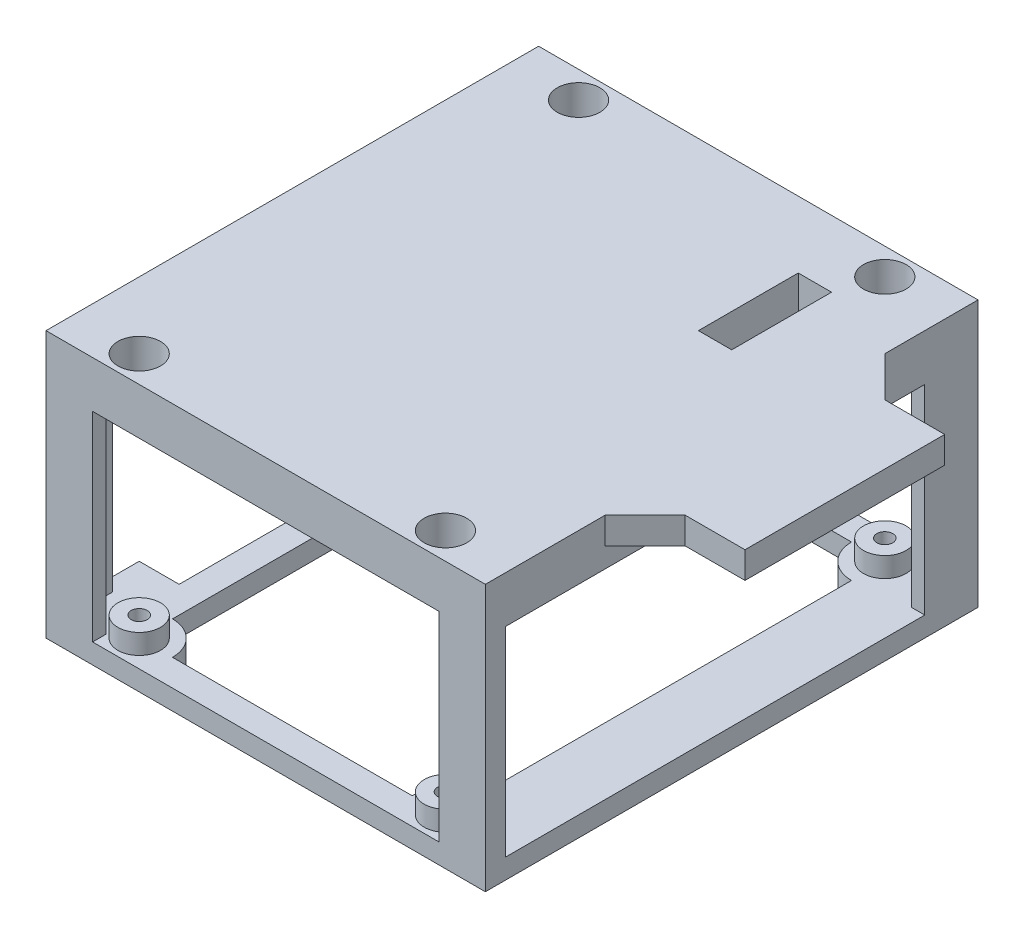
SolidWorks part; units mm, degrees
ref_plane "Front Plane" through (0, 0, 0) normal (0, 0, 1) x (1, 0, 0)
ref_plane "Top Plane" through (0, 0, 0) normal (0, 1, 0) x (1, 0, 0)
ref_plane "Right Plane" through (0, 0, 0) normal (1, 0, 0) x (0, 0, -1)
sketch "Sketch1" plane through (0, 0, 0) normal (0, 1, 0) x (1, 0, 0)
  line L0 (56, 70) -> (56, 4) construction
  line L1 (0, 0) -> (66, 0)
  line L2 (0, 0) -> (0, 74)
  line L3 (0, 74) -> (66, 74)
  line L4 (66, 0) -> (66, 74)
  line L5 (10, 4) -> (56, 4) construction
  line L6 (15, 70) -> (51, 70)
  line L11 (10, 65) -> (10, 9)
  line L12 (15, 4) -> (51, 4)
  line L13 (56, 65) -> (56, 9)
  line L14 (33, 74) -> (33, 0) construction
  line L19 (66, 54) -> (81, 54)
  line L20 (66, 54) -> (66, 24)
  line L21 (66, 24) -> (81, 24)
  line L22 (81, 54) -> (81, 24)
  line L23 (49, 64) -> (54, 64)
  line L24 (49, 64) -> (49, 49)
  line L25 (49, 49) -> (54, 49)
  line L26 (54, 64) -> (54, 49)
  line L28 (0, 60) -> (6, 60)
  line L29 (0, 60) -> (0, 14)
  line L30 (0, 14) -> (6, 14)
  line L31 (6, 60) -> (6, 14)
  circle A0 centre (10, 70) radius 1.2
  circle A1 centre (56, 70) radius 1.2
  circle A2 centre (10, 4) radius 1.2
  circle A3 centre (56, 4) radius 1.2
  circle A4 centre (10, 70) radius 3.2
  circle A5 centre (56, 70) radius 3.2
  circle A6 centre (10, 4) radius 3.2
  circle A7 centre (56, 4) radius 3.2
  arc A8 (10, 65) -> (15, 70) centre (10, 70) ccw
  arc A9 (51, 70) -> (56, 65) centre (56, 70) ccw
  arc A10 (56, 9) -> (51, 4) centre (56, 4) ccw
  arc A11 (15, 4) -> (10, 9) centre (10, 4) ccw
  point P13 (56, 37)
  point P14 (66, 37)
  point P15 (33, 4)
  point P16 (33, 0)
  dimension "D3" = 2.4
  dimension "D4" = 46
  dimension "D5" = 66
  dimension "D6" = 6.4
  dimension "D7" = 20
  dimension "D8" = 30
  dimension "D9" = 2
  dimension "D12" = 5
  dimension "D1" = 66
  dimension "D2" = 74
  dimension "D10" = 46
  dimension "D11" = 66
  dimension "D13" = 5
  dimension "D14" = 16
  dimension "D15" = 15
  dimension "D16" = 15
  dimension "D17" = 10
  dimension "D18" = 14
  dimension "D19" = 14
  dimension "D20" = 6
extrude "Main Outer Connection" add sketch "Sketch1" along normal blind 40 contours L1 L4 L3 L2 A3 A2 A1 A0 L12 A11 L11 A8 L6 A9 L13 A10 | A6 A2 | A7 A3 | A4 A0 | A5 A1 | L6 A9 L13 A10 L12 A11 L11 A8 | L29 L28 L31 L30 region at (0.9916, 0, -7) region at (6.8905, 0, -70) region at (52.8905, 0, -70) region at (6.8905, 0, -4) region at (52.8905, 0, -4)
sketch "Sketch2" plane through (0, 0, -74) normal (0, 0, -1) x (-1, 0, 0)
  line L1 (-64, 33) -> (-2, 33)
  line L2 (-64, 33) -> (-64, 3)
  line L3 (-64, 3) -> (-2, 3)
  line L4 (-2, 33) -> (-2, 3)
  line L5 (0, 40) -> (-66, 40) construction
  line L7 (-66, 40) -> (-66, 0) construction
  line L8 (0, 40) -> (0, 0) construction
  line L9 (0, 0) -> (-66, 0) construction
  dimension "D1" = 7
  dimension "D2" = 3
  dimension "D3" = 2
  dimension "D4" = 2
extrude "Hole for Protoboard Access" cut sketch "Sketch2" against normal through all
sketch "Sketch16" plane through (0, 0, 0) normal (0, 0, 1) x (1, 0, 0)
  line L0 (64, 3) -> (2, 3) construction
  line L1 (64, 33) -> (59, 33)
  line L2 (64, 33) -> (64, 3)
  line L3 (64, 3) -> (59, 3)
  line L4 (59, 33) -> (59, 3)
  line L6 (2, 33) -> (7, 33)
  line L7 (2, 33) -> (2, 3)
  line L8 (2, 3) -> (7, 3)
  line L9 (7, 33) -> (7, 3)
  dimension "D1" = 5
extrude "Wall for Screw Terminal Replace" add sketch "Sketch16" against normal blind 2 contours L4 L3 L2 L1 | L7 L6 L9 L8
sketch "Sketch18" plane through (66, 0, 0) normal (1, 0, 0) x (0, 0, -1)
  line L0 (0, 40) -> (0, 0) construction
  line L1 (3, 33) -> (66, 33)
  line L2 (3, 33) -> (3, 3)
  line L3 (3, 3) -> (66, 3)
  line L4 (66, 33) -> (66, 3)
  line L5 (74, 40) -> (74, 0) construction
  line L8 (0, 40) -> (74, 40) construction
  line L9 (3, 33) -> (8, 33)
  line L10 (3, 33) -> (3, 3)
  line L11 (3, 3) -> (8, 3)
  line L12 (8, 33) -> (8, 3)
  dimension "D1" = 3
  dimension "D2" = 8
  dimension "D4" = 7
  dimension "D5" = 8
extrude "Hole for Wire Connections" cut sketch "Sketch18" against normal through all contours L1 L12 L3 L4 region at (66, 18, -37)
extrude "Hole for Screw Terminal Replace" cut sketch "Sketch18<3>" against normal up to next contours L12 L1 L2 L3 region at (66, 18, -5.5)
sketch "Sketch18<3>" plane through (66, 0, 0) normal (1, 0, 0) x (0, 0, -1) same geometry as "Sketch18"
extrude "Hole for Wire in Bottom" cut sketch "Sketch1<3>" along normal blind 10 contours A11 L12 A10 L13 A9 L6 A8 L11 | L24 L25 L13 L23 | L29 L28 L31 L30 region at (32.5186, 0, -36.4926) region at (51.5, 0, -56.5)
sketch "Sketch1<3>" plane through (0, 0, 0) normal (0, 1, 0) x (1, 0, 0) same geometry as "Sketch1"
extrude "Bolt Head Clearance" cut sketch "Sketch1<5>" against normal up to surface (-33 mm away) from surface contours A7 A3 | A6 A2 | A4 A0 | A5 A1 region at (6.8905, 0, -70) region at (52.8905, 0, -70) region at (6.8905, 0, -4) region at (52.8905, 0, -4) up to face at (56, 33, -2.8) starting at face at (33, 40, -37)
sketch "Sketch1<5>" plane through (0, 0, 0) normal (0, 1, 0) x (1, 0, 0) same geometry as "Sketch1"
extrude "Standoff for Wire Clearance" add sketch "Sketch1<6>" along normal blind 3 from surface contours A6 A2 | A7 A3 | A5 A1 | A4 A0 region at (6.8905, 0, -70) region at (52.8905, 0, -70) region at (6.8905, 0, -4) region at (52.8905, 0, -4) starting at face at (33, 3, -37)
sketch "Sketch1<6>" plane through (0, 0, 0) normal (0, 1, 0) x (1, 0, 0) same geometry as "Sketch1"
extrude "Breakout Board Cover" add sketch "Sketch1<8>" against normal blind 4 from surface contours L22 L19 L4 L21 region at (73.5, 0, -39) starting at face at (56, 40, -66.8)
sketch "Sketch1<8>" plane through (0, 0, 0) normal (0, 1, 0) x (1, 0, 0) same geometry as "Sketch1"
extrude "Cut-Extrude14" cut sketch "Sketch1<9>" against normal up to surface (-33 mm away) from surface contours L26 L25 L24 L23 up to face at (56, 33, -66.8) starting at face at (56, 40, -66.8)
sketch "Sketch1<9>" plane through (0, 0, 0) normal (0, 1, 0) x (1, 0, 0) same geometry as "Sketch1"
chamfer "Chamfer2" distance 6 angle 45 2 edges at (66, 38, -54) (66, 38, -24)
